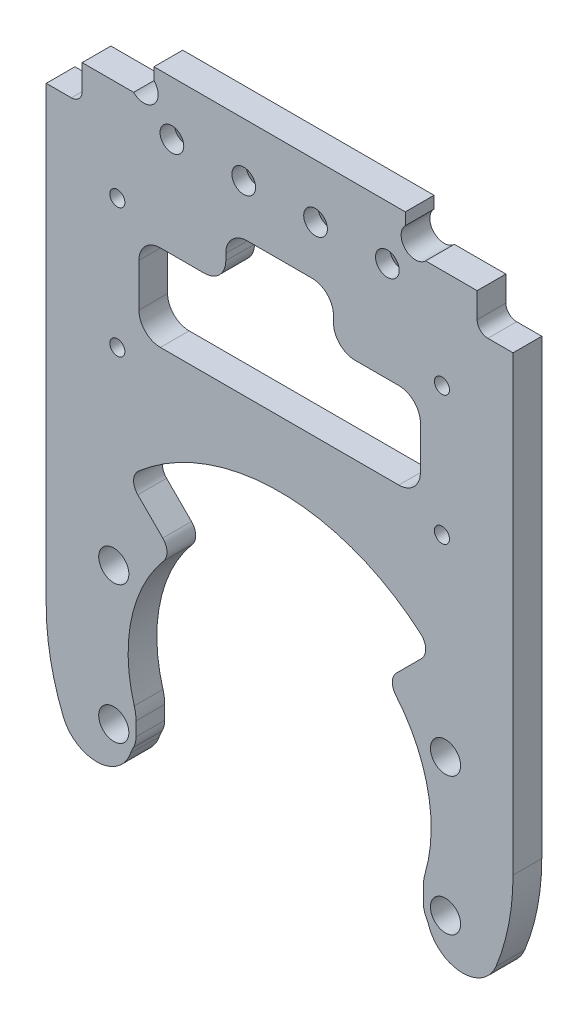
SolidWorks part; units mm, degrees
material "6061 合金"
ref_plane "前视基准面" through (0, 0, 0) normal (0, 0, 1) x (1, 0, 0)
ref_plane "上视基准面" through (0, 0, 0) normal (0, 1, 0) x (1, 0, 0)
ref_plane "右视基准面" through (0, 0, 0) normal (1, 0, 0) x (0, 0, -1)
other "边界框"
ref_plane "Default Plane" through (35, -17.1362, 0) normal (-1, 0, 0) x (0, 0, 1)
other "Configuration Table"
sketch "草图1" plane through (0, 0, 0) normal (0, 0, 1) x (1, 0, 0)
  line L0 (-32.5, 80) -> (32.5, 80)
  line L1 (-32.5, 80) -> (-32.5, 0)
  line L2 (32.5, 80) -> (32.5, 0)
  line L3 (-32.5, 0) -> (32.5, 0)
  line L4 (-32.5, 80) -> (32.5, 0) construction
  line L5 (32.5, 80) -> (-32.5, 0) construction
  circle A0 centre (0, 0) radius 32.5
  circle A1 centre (0, 0) radius 50 construction
  point P4 (0, 40)
  dimension "D1" = 65
  dimension "D2" = 100
  dimension "D3" = 80
extrude "凸台-拉伸1" add sketch "草图1" along normal blind 4 contours A0 L2 L0 L1 | L3 A0 | L3 A0
sketch "草图2" plane through (0, 0, 4) normal (0, 0, 1) x (1, 0, 0)
  line L0 (-21.1, 0) -> (21.1, 0)
  line L1 (-21.1, 0) -> (-21.1, -49.6978)
  line L2 (21.1, 0) -> (21.1, -49.6978)
  line L3 (-21.1, -49.6978) -> (21.1, -49.6978)
  circle A0 centre (0, 0) radius 21.1
  dimension "D1" = 42.2
extrude "切除-拉伸1" cut sketch "草图2" against normal through all both contours L0 A0 | L0 A0
sketch "草图3" plane through (0, 0, 4) normal (0, 0, 1) x (1, 0, 0)
  line L0 (0, 0) -> (50000, 0) construction
  line L1 (0, -0.6232) -> (0, -50000.6232) construction
  line L2 (9.5671, 23.097) -> (0, 0) construction
  circle A0 centre (0, 0) radius 25 construction
  circle A1 centre (9.5671, 23.097) radius 1.65
  dimension "D1" = 50
  dimension "D2" = 3.3
  dimension "D3" = 22.5
extrude "切除-拉伸2" cut sketch "草图3" against normal through all both
pattern_circular "阵列(圆周)1" count 8 over 360 about axis through (0, 0, 0) along (0, 0, 1) of "切除-拉伸2"
sketch "草图4" plane through (0, 0, 4) normal (0, 0, 1) x (1, 0, 0)
  line L0 (-20, -9.5671) -> (20, -9.5671) construction
  line L1 (-20, -9.5671) -> (-20, 6.7238)
  line L2 (20, -9.5671) -> (20, 6.7238)
  circle A0 centre (-23.097, -9.5671) radius 3.097
  circle A1 centre (0, 0) radius 21.903
  circle A2 centre (0, 0) radius 28.097
  circle A3 centre (23.097, -9.5671) radius 3.097
  circle A4 centre (0, 0) radius 21.1
  arc A5 (21.1, 0) -> (-21.1, 0) centre (0, 0) ccw construction
  line M12 (21.1, 0) -> (21.1, -24.7192)
  line M18 (-21.1, -24.7192) -> (-21.1, 0)
  dimension "D1" = 40
extrude "凸台-拉伸2" add sketch "草图4" against normal blind 4 contours A3 M12 | A3 A1 L2 | A4 L2 A1 M12 | A3 A1 M12 | A0 M18 | A1 A0 M18 | A4 A1 L1 M18 | A1 A0 L1 | A2
fillet "圆角1" radius 6 4 edges at (21.1, -11.9342, 2) (-21.1, -11.9342, 2) (-20, -6.7238, 2) (20, -6.7238, 2)
sketch "草图6" plane through (0, 0, 4) normal (0, 0, 1) x (1, 0, 0)
  line L0 (0, 0) -> (0, 50000) construction
  line L1 (0, 0) -> (-21.2132, 21.2132)
  line L2 (0, 0) -> (21.2132, 21.2132)
  circle A0 centre (0, 0) radius 30
  circle M4 centre (-9.5671, 23.097) radius 1.65
  circle M9 centre (9.5671, 23.097) radius 1.65
  arc M23 (-20.2435, -5.9505) -> (20.2435, -5.9505) centre (0, 0) cw
  dimension "D1" = 60
  dimension "D2" = 45
extrude "切除-拉伸3" cut sketch "草图6" against normal through all both contours L0 L2 A0 M23 M9 | L0 A0 L1 M23 M4 | L1 L0 M23 | L0 L2 M23
fillet "圆角2" radius 2 4 edges at (14.92, 14.92, 2) (21.2132, 21.2132, 2) (-14.92, 14.92, 2) (-21.2132, 21.2132, 2)
sketch "草图7" plane through (0, 0, 4) normal (0, 0, 1) x (1, 0, 0)
  line L0 (-32.5, 68) -> (32.5, 68)
  line L1 (0, 0) -> (0, 50) construction
  line L2 (0, 50) -> (0, 68) construction
  line L3 (32.5, 80) -> (32.5, 0) construction
  line L4 (-17.5, 72.5) -> (17.5, 72.5)
  line L5 (-17.5, 72.5) -> (-17.5, 68)
  line L6 (17.5, 72.5) -> (17.5, 68)
  line L7 (-17.5, 68) -> (17.5, 68)
  line L8 (-17.5, 72.5) -> (17.5, 68) construction
  line L9 (17.5, 72.5) -> (-17.5, 68) construction
  line L17 (32.5, 0) -> (32.5, 80)
  line L18 (32.5, 80) -> (-32.5, 80)
  line L19 (-32.5, 80) -> (-32.5, 0)
  line L22 (32.5, 0) -> (32.5, 80)
  line L23 (32.5, 80) -> (-32.5, 80)
  line L24 (-32.5, 80) -> (-32.5, 0)
  line L27 (-20, -9.5671) -> (-20, -7.6426)
  line L29 (-20, -9.5671) -> (-20, -7.6426)
  line L31 (20, -7.6426) -> (20, -9.5671)
  line L32 (20, -7.6426) -> (20, -9.5671)
  line L33 (21.1, -13.9034) -> (21.1, -24.7192)
  line L34 (21.1, -13.9034) -> (21.1, -24.7192)
  line L35 (-21.1, -24.7192) -> (-21.1, -13.9034)
  line L36 (-21.1, -24.7192) -> (-21.1, -13.9034)
  line L37 (19.7484, 19.7484) -> (16.2728, 16.2728)
  line L38 (19.7484, 19.7484) -> (16.2728, 16.2728)
  line L39 (-16.2728, 16.2728) -> (-19.7484, 19.7484)
  line L40 (-16.2728, 16.2728) -> (-19.7484, 19.7484)
  circle A0 centre (0, 0) radius 50 construction
  arc A4 (-20.3745, -11.0433) -> (-21.1, -13.9034) centre (-15.1, -13.9034) ccw
  arc A12 (-32.5, 0) -> (-21.1, -24.7192) centre (0, 0) ccw
  arc A19 (-20.3745, -11.0433) -> (-21.1, -13.9034) centre (-15.1, -13.9034) ccw
  arc A20 (-20.3745, -11.0433) -> (-20, -9.5671) centre (-23.097, -9.5671) ccw
  arc A21 (-20.3745, -11.0433) -> (-20, -9.5671) centre (-23.097, -9.5671) ccw
  arc A22 (21.1, -24.7192) -> (32.5, 0) centre (0, 0) ccw
  arc A23 (-32.5, 0) -> (-21.1, -24.7192) centre (0, 0) ccw
  arc A33 (21.1, -24.7192) -> (32.5, 0) centre (0, 0) ccw
  arc A34 (-20, -7.6426) -> (-20.2435, -5.9505) centre (-26, -7.6426) ccw
  arc A35 (-20, -7.6426) -> (-20.2435, -5.9505) centre (-26, -7.6426) ccw
  arc A36 (-16.1557, 13.5722) -> (-20.2435, -5.9505) centre (0, 0) ccw
  arc A38 (-16.1557, 13.5722) -> (-20.2435, -5.9505) centre (0, 0) ccw
  arc A40 (20.2435, -5.9505) -> (20, -7.6426) centre (26, -7.6426) ccw
  arc A41 (20.2435, -5.9505) -> (20, -7.6426) centre (26, -7.6426) ccw
  arc A42 (20, -9.5671) -> (20.3745, -11.0433) centre (23.097, -9.5671) ccw
  arc A43 (20, -9.5671) -> (20.3745, -11.0433) centre (23.097, -9.5671) ccw
  arc A44 (21.1, -13.9034) -> (20.3745, -11.0433) centre (15.1, -13.9034) ccw
  arc A46 (21.1, -13.9034) -> (20.3745, -11.0433) centre (15.1, -13.9034) ccw
  arc A48 (20.2435, -5.9505) -> (16.1557, 13.5722) centre (0, 0) ccw
  arc A50 (20.2435, -5.9505) -> (16.1557, 13.5722) centre (0, 0) ccw
  arc A52 (19.6438, 22.6742) -> (-19.6438, 22.6742) centre (0, 0) ccw
  arc A53 (19.6438, 22.6742) -> (-19.6438, 22.6742) centre (0, 0) ccw
  arc A54 (16.2728, 16.2728) -> (16.1557, 13.5722) centre (17.687, 14.8586) ccw
  arc A55 (16.2728, 16.2728) -> (16.1557, 13.5722) centre (17.687, 14.8586) ccw
  arc A56 (-16.1557, 13.5722) -> (-16.2728, 16.2728) centre (-17.687, 14.8586) ccw
  arc A57 (-16.1557, 13.5722) -> (-16.2728, 16.2728) centre (-17.687, 14.8586) ccw
  arc A58 (-19.6438, 22.6742) -> (-19.7484, 19.7484) centre (-18.3342, 21.1626) ccw
  arc A59 (-19.6438, 22.6742) -> (-19.7484, 19.7484) centre (-18.3342, 21.1626) ccw
  arc A60 (19.7484, 19.7484) -> (19.6438, 22.6742) centre (18.3342, 21.1626) ccw
  arc A61 (19.7484, 19.7484) -> (19.6438, 22.6742) centre (18.3342, 21.1626) ccw
  point P12 (0, 70.25)
  line M43 (32.5, 0) -> (32.5, 80)
  line M44 (32.5, 80) -> (-32.5, 80)
  line M45 (-32.5, 80) -> (-32.5, 0)
  dimension "D1" = 100
  dimension "D2" = 18
  dimension "D3" = 35
  dimension "D4" = 4.5
  dimension "D5" = 0
extrude "切除-拉伸4" cut sketch "草图7" against normal through all contours L4 L6 L0 L5 M43 M44 M45
sketch "草图8" plane through (0, 0, 4) normal (0, 0, 1) x (1, 0, 0)
  line L2 (-18.9142, 69.4142) -> (-17.5, 68) construction
  line L3 (-32.5, 68) -> (-17.5, 68) construction
  circle A0 centre (-18.9142, 69.4142) radius 2
  circle A1 centre (18.9142, 69.4142) radius 2
  dimension "D1" = 4
  dimension "D2" = 45
extrude "切除-拉伸5" cut sketch "草图8" against normal through all
sketch "草图9" plane through (0, 0, 4) normal (0, 0, 1) x (1, 0, 0)
  line L0 (-35, 68) -> (49965, 68) construction
  line L1 (0, 0) -> (0, 50000) construction
  line L2 (-6.6399, 65) -> (49993.3601, 65) construction
  line L3 (-15, 65) -> (-5, 65) construction
  line L4 (-5, 65) -> (5, 65) construction
  line L5 (5, 65) -> (15, 65) construction
  circle A0 centre (5, 65) radius 1.65
  circle A1 centre (15, 65) radius 1.65
  circle A2 centre (-5, 65) radius 1.65
  circle A3 centre (-15, 65) radius 1.65
  dimension "D2" = 3.3
  dimension "D1" = 3
  dimension "D3" = 10
extrude "切除-拉伸6" cut sketch "草图9" against normal through all both
sketch "草图21" plane through (-123.7424, -19.3884, 4) normal (0, 0, 1) x (1, 0, 0)
  line L0 (123.7424, 73.4884) -> (123.7424, 64.4884) construction
  line L1 (101.1424, 73.4884) -> (146.3424, 73.4884) construction
  line L2 (101.1424, 73.4884) -> (101.1424, 55.4884) construction
  line L3 (101.1424, 55.4884) -> (146.3424, 55.4884) construction
  line L4 (146.3424, 73.4884) -> (146.3424, 55.4884) construction
  line L5 (101.1424, 73.4884) -> (146.3424, 55.4884) construction
  line L6 (101.1424, 55.4884) -> (146.3424, 73.4884) construction
  line L7 (123.7424, 64.4884) -> (146.3424, 64.4884) construction
  line L8 (-1290.4035, 64.4884) -> (48709.5965, 64.4884) construction
  line L9 (123.7424, 1173.4506) -> (123.7424, 51173.4506) construction
  line L10 (144.0709, 87.3884) -> (156.2424, 87.3884) construction
  line L11 (148.4424, 77.3884) -> (148.4424, 51.5884) construction
  line L12 (148.4424, 77.3884) -> (99.0424, 77.3884) construction
  line L13 (99.0424, 77.3884) -> (99.0424, 51.5884) construction
  line L14 (148.4424, 51.5884) -> (99.0424, 51.5884) construction
  line L15 (148.4424, 77.3884) -> (99.0424, 51.5884) construction
  line L16 (99.0424, 77.3884) -> (148.4424, 51.5884) construction
  circle A4 centre (146.3424, 55.4884) radius 1.05
  circle A5 centre (101.1424, 55.4884) radius 1.05
  circle A6 centre (101.1424, 73.4884) radius 1.05
  circle A7 centre (146.3424, 73.4884) radius 1.05
  point P5 (123.7424, 64.4884)
  point P13 (123.7424, 64.4884)
  dimension "D1" = 2.1
  dimension "D2" = 45.2
  dimension "D3" = 18
  dimension "D4" = 25.8
  dimension "D5" = 3.9
  dimension "D6" = 49.4
  dimension "D7" = 10
extrude "C620孔位" cut sketch "草图21" against normal through all
other "C620螺栓M2安装孔位<1>"
chamfer "倒角2" distance 2 angle 45 4 edges at (-13.35, 65, 0) (16.65, 65, 0) (6.65, 65, 0) (-3.35, 65, 0)
fillet "圆角3" radius 5 4 edges at (21.1, -19.3113, 0) (21.1, -19.3113, 4) (21.1, -13.9034, 2) (21.1, -24.7192, 2)
fillet "圆角4" radius 5 4 edges at (-21.1, -19.3113, 4) (-21.1, -19.3113, 0) (-21.1, -13.9034, 2) (-21.1, -24.7192, 2)
sketch "草图22" plane through (0, 0, 4) normal (0, 0, 1) x (1, 0, 0)
  line L0 (-22.6, 54.1) -> (22.6, 54.1) construction
  line L1 (-22.6, 54.1) -> (-22.6, 36.1) construction
  line L2 (22.6, 54.1) -> (22.6, 36.1) construction
  line L3 (-22.6, 36.1) -> (22.6, 36.1) construction
  line L4 (-19.6, 39.1) -> (19.6, 39.1)
  line L5 (19.6, 51.1) -> (19.6, 39.1)
  line L6 (-19.6, 51.1) -> (19.6, 51.1)
  line L7 (-19.6, 51.1) -> (-19.6, 39.1)
  line L8 (-7.5, 58) -> (7.5, 58)
  line L9 (-7.5, 58) -> (-7.5, 51.1)
  line L10 (7.5, 58) -> (7.5, 51.1)
  line L11 (-7.5, 51.1) -> (7.5, 51.1)
  line L12 (-7.5, 58) -> (7.5, 51.1) construction
  line L13 (7.5, 58) -> (-7.5, 51.1) construction
  line L14 (-20, 68) -> (-20, 62) construction
  line L15 (-20, 68) -> (20, 68) construction
  line L16 (-20, 62) -> (20, 62) construction
  line L17 (20, 68) -> (20, 62) construction
  line L18 (-20, 68) -> (20, 62) construction
  line L19 (-20, 62) -> (20, 68) construction
  line L20 (-32.5, 68) -> (-20.3284, 68) construction
  circle A0 centre (22.6, 36.1) radius 1.05 construction
  point P13 (0, 54.55)
  point P14 (0, 65)
  dimension "D2" = 15
  dimension "D3" = 40
  dimension "D4" = 6
  dimension "D5" = 4
  dimension "D1" = 3
extrude "切除-拉伸7" cut sketch "草图22" against normal through all both and the other way through all contours L6 L7 L4 L5 | L10 L8 L9 L6
fillet "圆角5" radius 3 8 edges at (-19.6, 51.1, 2) (-7.5, 51.1, 2) (-7.5, 58, 2) (7.5, 58, 2) (7.5, 51.1, 2) (19.6, 51.1, 2) (19.6, 39.1, 2) (-19.6, 39.1, 2)
sketch "草图23" plane through (0, 0, 4) normal (0, 0, 1) x (1, 0, 0)
  circle A0 centre (23.097, 9.5671) radius 2.1
  circle A1 centre (23.097, -9.5671) radius 2.1
  circle A2 centre (-23.097, 9.5671) radius 2.1
  circle A3 centre (-23.097, -9.5671) radius 2.1
  dimension "D1" = 4.2
extrude "切除-拉伸8" cut sketch "草图23" against normal through all both
sketch "草图24" plane through (0, 0, 0) normal (0, 0, -1) x (-1, 0, 0)
  line L0 (32.5, 68) -> (27.5, 68)
  line L1 (32.5, 68) -> (32.5, 63)
  line L2 (27.5, 68) -> (27.5, 63)
  line L3 (32.5, 63) -> (27.5, 63)
  line L4 (32.5, 68) -> (20.3284, 68) construction
  line L5 (-32.5, 68) -> (-27.5, 68)
  line L6 (-32.5, 68) -> (-32.5, 63)
  line L7 (-27.5, 68) -> (-27.5, 63)
  line L8 (-32.5, 63) -> (-27.5, 63)
  dimension "D1" = 5
  dimension "D2" = 5
extrude "切除-拉伸9" cut sketch "草图24" against normal through all both and the other way through all
fillet "圆角6" radius 1.5 2 edges at (27.5, 63, 2) (-27.5, 63, 2)
